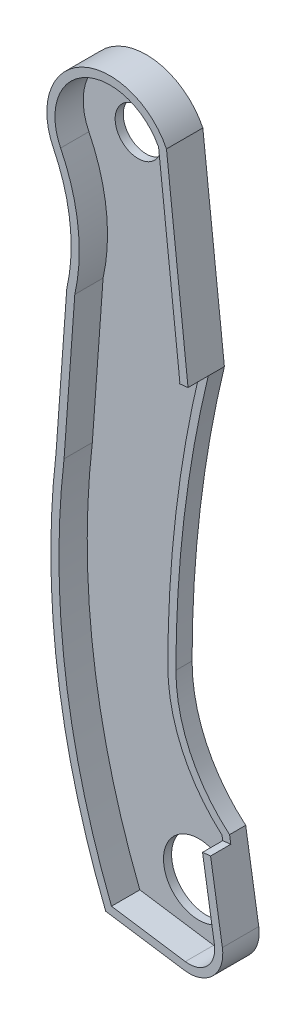
SolidWorks part; units mm, degrees
material "Plain Carbon Steel"
ref_plane "Front Plane" through (0, 0, 0) normal (0, 0, 1) x (1, 0, 0)
ref_plane "Top Plane" through (0, 0, 0) normal (0, 1, 0) x (1, 0, 0)
ref_plane "Right Plane" through (0, 0, 0) normal (1, 0, 0) x (0, 0, -1)
sketch "Sketch1" plane through (0, 0, 0) normal (0, 0, 1) x (1, 0, 0)
  line L0 (23.3836, 52.613) -> (116.9178, 52.613) construction
  line L1 (62.695, 80.6597) -> (64.727, 62.1939)
  line L4 (66.7362, 25.7472) -> (68.6523, 13.8092)
  line L5 (56.9683, 15.5537) -> (68.6523, 13.8092)
  line L6 (53.297, 64.5757) -> (52.281, 50.6057)
  arc A0 (62.695, 80.6597) -> (52.031, 75.4076) centre (57.361, 78.0377) ccw
  arc A1 (53.297, 64.5757) -> (52.031, 75.4076) centre (37.4533, 68.2139) ccw
  arc A3 (52.281, 50.6057) -> (56.9683, 15.5537) centre (123.4234, 42.2798) ccw
  arc A6 (61.679, 36.6357) -> (66.7362, 25.7472) centre (75.903, 36.6234) ccw
  arc A7 (64.727, 62.1939) -> (61.679, 36.6357) centre (171.1529, 36.541) ccw
  dimension "D1" = 5.334
  dimension "D2" = 7.366
  dimension "D3" = 18.4658
  dimension "D4" = 5.9436
  dimension "D5" = 109.474
  dimension "D6" = 14.224
  dimension "D7" = 41.402
  dimension "D12" = 71.628
  dimension "D15" = 16.256
  dimension "D8" = 4.318
  dimension "D9" = 11.938
  dimension "D10" = 11.684
  dimension "D11" = 62.484
  dimension "D13" = 27.432
  dimension "D14" = 5.08
  dimension "D16" = 13.97
  dimension "D17" = 4.064
extrude "Boss-Extrude1" add sketch "Sketch1" along normal blind 3.429
fillet "Fillet1" radius 3.175 1 edges at (68.6523, 13.8092, 1.7145)
shell "Shell1" thickness 0.762 removed face at (59.7815, 44.769, 3.429)
sketch "Sketch2" plane through (0, 0, 3.429) normal (0, 0, 1) x (1, 0, 0)
  line L2 (67.9647, 18.0933) -> (66.7362, 25.7472) construction
  line L3 (56.9683, 15.5537) -> (64.3609, 14.45) construction
  circle A0 centre (57.361, 78.0377) radius 2.1717
  circle A1 centre (63.0729, 19.8813) radius 3.3274
  dimension "D1" = 4.3434
  dimension "D2" = 4.5466
  dimension "D4" = 6.6548
  dimension "D3" = 5.1816
extrude "Cut-Extrude1" cut sketch "Sketch2" against normal through all
sketch "Sketch4" plane through (70.7146, 7.7815, 0) normal (0.994, 0.1094, 0) x (0, 0, -1)
  line L0 (-3.429, 54.7409) -> (0, 54.7409) construction
  line L1 (-3.429, 54.7409) -> (-1.524, 54.7409)
  line L2 (-3.429, 54.7409) -> (-3.429, 17.5553)
  line L3 (-3.429, 17.5553) -> (-1.524, 17.5553)
  line L4 (-1.524, 54.7409) -> (-1.524, 17.5553)
  line L5 (-3.429, 54.7409) -> (-3.429, 73.3181) construction
  line L6 (0, 54.7409) -> (0, 73.3181) construction
  line L7 (-3.429, 10.5507) -> (-3.429, 18.2931) construction
  line L8 (-3.429, 73.3181) -> (0, 73.3181) construction
  dimension "D1" = 1.524
  dimension "D2" = 37.1856
extrude "Cut-Extrude3" cut sketch "Sketch4" against normal blind 8.509
